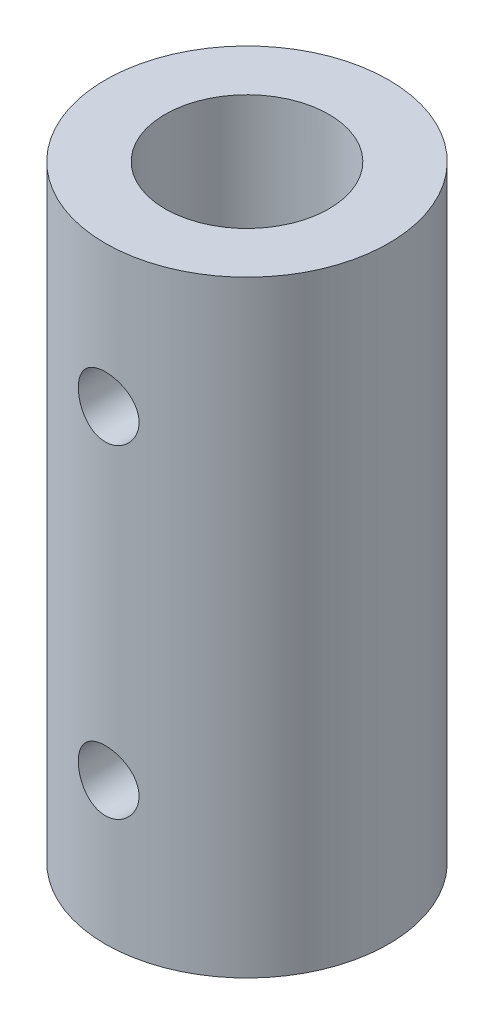
SolidWorks part; units mm, degrees
ref_plane "Front Plane" through (0, 0, 0) normal (0, 0, 1) x (1, 0, 0)
ref_plane "Top Plane" through (0, 0, 0) normal (0, 1, 0) x (1, 0, 0)
ref_plane "Right Plane" through (0, 0, 0) normal (1, 0, 0) x (0, 0, -1)
sketch "Sketch1" plane through (0, 0, 0) normal (0, 1, 0) x (1, 0, 0)
  circle A0 centre (0, 0) radius 7
  circle A1 centre (0, 0) radius 4.05
  circle A2 centre (0, 0) radius 2.55
  dimension "D1" = 8.1
  dimension "D2" = 14
  dimension "D3" = 5.1
extrude "Boss-Extrude1" add sketch "Sketch1" along normal blind 15 contours A0 A1 region at (-6.802, 0, 0)
extrude "Boss-Extrude2" add sketch "Sketch1<3>" against normal blind 15 contours A0 A1 | A1 A2 region at (-6.802, 0, 0) region at (-3.9354, 0, 0)
sketch "Sketch1<3>" plane through (0, 0, 0) normal (0, 1, 0) x (1, 0, 0) same geometry as "Sketch1"
sketch "Sketch2" plane through (0, 0, 0) normal (0, 0, 1) x (1, 0, 0)
  line L0 (-7, -15) -> (7, -15) construction
  line L1 (4.05, 15) -> (-4.05, 15) construction
  circle A0 centre (0, 8) radius 1.5
  circle A1 centre (0, -8) radius 1.5
  dimension "D1" = 3
  dimension "D2" = 3
  dimension "D3" = 7
  dimension "D4" = 7
extrude "Cut-Extrude1" cut sketch "Sketch2" against normal through all both and the other way through all
